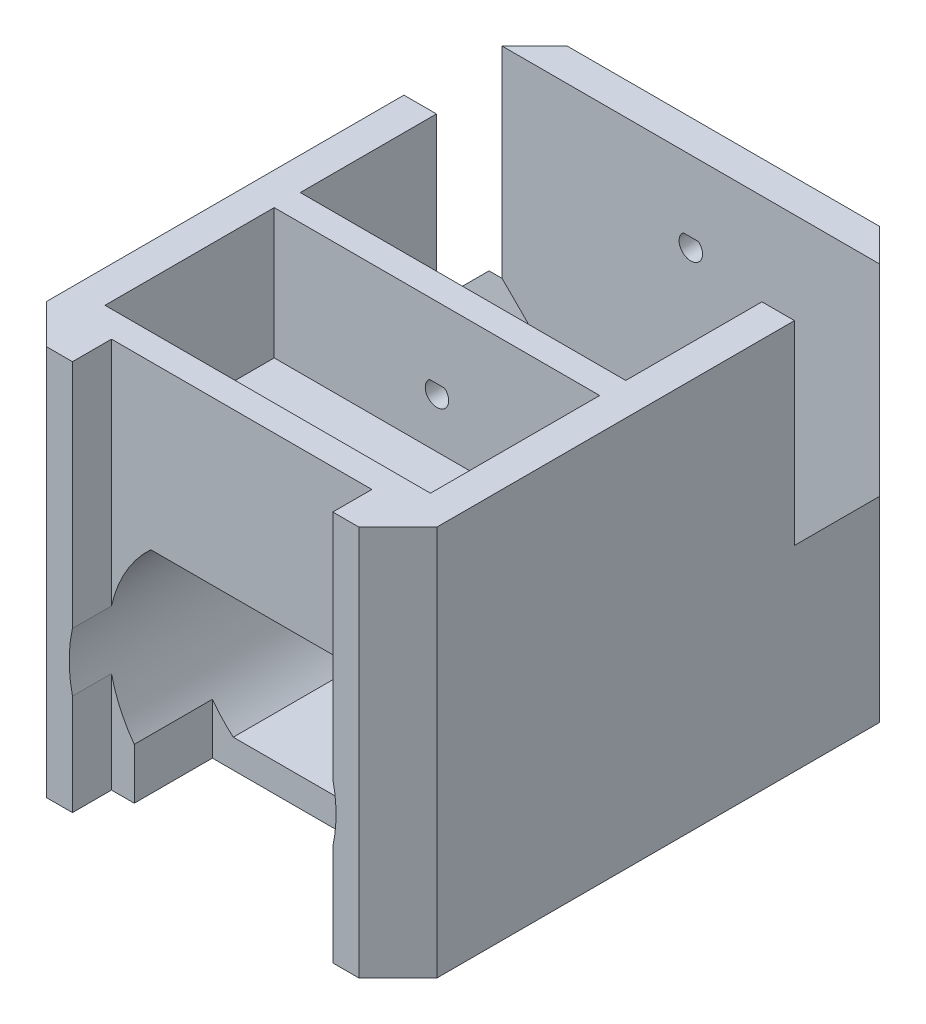
SolidWorks part; units mm, degrees
ref_plane "Front Plane" through (0, 0, 0) normal (0, 0, 1) x (1, 0, 0)
ref_plane "Top Plane" through (0, 0, 0) normal (0, 1, 0) x (1, 0, 0)
ref_plane "Right Plane" through (0, 0, 0) normal (1, 0, 0) x (0, 0, -1)
sketch "Sketch1" plane through (0, 0, 0) normal (0, 0, 1) x (1, 0, 0)
  line L1 (-15, -20) -> (15, -20)
  line L2 (-15, -20) -> (-15, 20)
  line L3 (-15, 20) -> (15, 20)
  line L4 (15, -20) -> (15, 20)
  line L5 (-15, -20) -> (15, 20) construction
  line L6 (-15, 20) -> (15, -20) construction
  point P0 (0, 0)
  dimension "D1" = 30
  dimension "D2" = 40
extrude "Boss-Extrude1" add sketch "Sketch1" along normal blind 40
sketch "Sketch2" plane through (0, 0, 40) normal (0, 0, 1) x (1, 0, 0)
  line L5 (-6.9866, -2.5) -> (6.9866, -2.5)
  line L7 (-6.6464, -17.803) -> (6.6464, -17.803)
  arc A4 (-6.9866, -2.5) -> (-6.6464, -17.803) centre (0, -10) ccw
  arc A5 (6.6464, -17.803) -> (6.9866, -2.5) centre (0, -10) ccw
  point P0 (0, -10)
  dimension "D2" = 20.5
extrude "Cut-Extrude1" cut sketch "Sketch2" against normal blind 35
sketch "Sketch4" plane through (0, 20, 0) normal (0, 1, 0) x (1, 0, 0)
  line L1 (-12.5, -37.5) -> (12.5, -37.5)
  line L2 (-12.5, -37.5) -> (-12.5, -2.5)
  line L3 (-12.5, -2.5) -> (12.5, -2.5)
  line L4 (12.5, -37.5) -> (12.5, -2.5)
  point P0 (0, -20)
  dimension "D1" = 25
  dimension "D2" = 35
extrude "Cut-Extrude3" cut sketch "Sketch4" against normal blind 20
sketch "Sketch5" plane through (0, 0, 0) normal (0, 1, 0) x (1, 0, 0)
  line L0 (12.5, -37.5) -> (12.5, -2.5) construction
  line L1 (-12.5, -2.5) -> (12.5, -2.5)
  line L2 (-12.5, -2.5) -> (-12.5, -20)
  line L3 (-12.5, -20) -> (12.5, -20)
  line L4 (12.5, -2.5) -> (12.5, -20)
extrude "Cut-Extrude4" cut sketch "Sketch5" against normal blind 20
sketch "Sketch13" plane through (0, 0, 0) normal (0, 1, 0) x (1, 0, 0)
  line L0 (12.5, -37.5) -> (12.5, -20) construction
  line L1 (-12.5, -20) -> (12.5, -20)
  line L2 (-12.5, -20) -> (-12.5, -22.0007)
  line L3 (-12.5, -22.0007) -> (12.5, -22.0007)
  line L4 (12.5, -20) -> (12.5, -22.0007)
extrude "Boss-Extrude3" add sketch "Sketch13" along normal up to surface (20 mm away) up to face at (0, 20, 20)
sketch "Sketch8" plane through (0, 0, 40) normal (0, 0, 1) x (1, 0, 0)
  line L0 (-0.5467, -9.1627) -> (0.5467, -9.1627)
  arc A3 (-0.5467, -9.1627) -> (0.5467, -9.1627) centre (0, -10.2278) ccw
extrude "Cut-Extrude5" cut sketch "Sketch8" against normal up to surface (40 mm away) up to face at (0, 0, 0)
sketch "Sketch9" plane through (0, 0, 0) normal (0, 0, -1) x (-1, 0, 0)
  line L5 (-0.5842, 4.5346) -> (0.5842, 4.5346)
  arc A0 (-0.5842, 4.5346) -> (0.5842, 4.5346) centre (0, 3.85) ccw
  dimension "D2" = 1.8
extrude "Cut-Extrude6" cut sketch "Sketch9" against normal up to surface (40 mm away) up to face at (0, -10.1897, 40)
sketch "Sketch10" plane through (0, 0, 40) normal (0, 0, 1) x (1, 0, 0)
  line L0 (15, -20) -> (15, 20) construction
  line L1 (-15, 20) -> (15, 20)
  line L2 (-15, 20) -> (-15, 10)
  line L3 (-15, 10) -> (15, 10)
  line L4 (15, 20) -> (15, 10)
  dimension "D1" = 10
extrude "Cut-Extrude9" cut sketch "Sketch10" against normal up to surface (40 mm away) up to face at (0, 3.7423, 0)
chamfer "Chamfer2" distance 3 angle 45 4 edges at (15, -5, 0) (15, -5, 40) (-15, -5, 40) (-15, -5, 0)
sketch "Sketch16" plane through (-12.5, 0, 0) normal (1, 0, 0) x (0, 0, -1)
  line L1 (-2.5, 10) -> (-9.5368, 10)
  line L2 (-2.5, 10) -> (-2.5, -4.4568)
  line L4 (-9.5368, 10) -> (-9.5368, -4.4568)
  line L5 (-9.5368, -4.4568) -> (-2.5, -4.4568)
extrude "Cut-Extrude10" cut sketch "Sketch16" against normal mid plane 57
chamfer "Chamfer3" distance 3 angle 45 2 edges at (12.5, -4.4568, 6.0184) (-12.5, -4.4568, 6.0184)
sketch "Sketch17" plane through (0, 10, 0) normal (0, 1, 0) x (1, 0, 0)
  line L0 (12.5, -37.5) -> (12.5, -22.0007) construction
  line L1 (-12.5, -37.5) -> (12.5, -37.5)
  line L2 (-12.5, -37.5) -> (-12.5, -35)
  line L3 (-12.5, -35) -> (12.5, -35)
  line L4 (12.5, -37.5) -> (12.5, -35)
  dimension "D1" = 2.5
extrude "Boss-Extrude4" add sketch "Sketch17" against normal up to surface (10 mm away) up to face at (0, 0, 29.7504)
sketch "Sketch18" plane through (0, 10, 0) normal (0, 1, 0) x (1, 0, 0)
  line L0 (-10, -40) -> (10, -40)
  line L1 (-12, -40) -> (12, -40) construction
  line L5 (-10, -40) -> (10, -40)
  line L6 (-10, -40) -> (-10, -37)
  line L7 (-10, -37) -> (10, -37)
  line L8 (10, -40) -> (10, -37)
  point P5 (0, -40)
  line M15 (-12, -40) -> (12, -40)
  dimension "D1" = 20
  dimension "D2" = 3
extrude "Cut-Extrude13" cut sketch "Sketch18" against normal up to surface (30 mm away) contours L8 L7 L6 M15 region at (0, 10, 38.5) up to face at (0, -20, 11.25)
sketch "Sketch19" plane through (0, -20, 0) normal (0, -1, 0) x (1, 0, 0)
  line L0 (-8.25, 37) -> (8.25, 37)
  line L1 (10, 37) -> (-10, 37) construction
  line L5 (-8.25, 37) -> (8.25, 37)
  line L6 (-8.25, 37) -> (-8.25, 31)
  line L7 (-8.25, 31) -> (8.25, 31)
  line L8 (8.25, 37) -> (8.25, 31)
  point P5 (0, 37)
  line M18 (10, 37) -> (-10, 37)
  dimension "D1" = 16.5
  dimension "D2" = 6
extrude "Cut-Extrude14" cut sketch "Sketch19" against normal blind 10 contours L8 L6 L7 M18 region at (0, -20, 34)
sketch "Sketch20" plane through (0, 0, 20) normal (0, 0, -1) x (-1, 0, 0)
  line L0 (10.25, -10) -> (12.5, -10)
  line L1 (-12.5, -10) -> (-10.25, -10)
  line L2 (-12.5, -10) -> (-12.5, -20)
  line L3 (-12.5, -20) -> (12.5, -20)
  line L4 (12.5, -20) -> (12.5, 10)
  line L5 (12.5, 10) -> (-12.5, 10)
  line L6 (-12.5, 10) -> (-12.5, -20)
  line L7 (-12.5, -20) -> (12.5, -20)
  line L8 (12.5, -20) -> (12.5, -10)
  line L10 (-12.5, -10) -> (-12.5, -20)
  line L11 (-12.5, -20) -> (12.5, -20)
  line L12 (12.5, -10) -> (12.5, -20)
  line L13 (-6.6464, -17.803) -> (6.6464, -17.803)
  arc A0 (6.6464, -17.803) -> (6.9866, -2.5) centre (0, -10) ccw construction
  arc A1 (6.6464, -17.803) -> (10.25, -10) centre (0, -10) ccw
  arc A2 (-6.9866, -2.5) -> (-6.6464, -17.803) centre (0, -10) ccw construction
  arc A3 (-10.25, -10) -> (-6.6464, -17.803) centre (0, -10) ccw
  line M7 (12.5, -20) -> (12.5, 10)
  line M9 (-12.5, 10) -> (-12.5, -20)
  line M10 (-12.5, -20) -> (12.5, -20)
  line M11 (6.6464, -17.803) -> (-6.6464, -17.803)
  arc M12 (-6.6464, -17.803) -> (-6.9866, -2.5) centre (0, -10) cw
  arc M14 (6.9866, -2.5) -> (6.6464, -17.803) centre (0, -10) cw
  dimension "D1" = 0
extrude "Boss-Extrude5" add sketch "Sketch20" along normal blind 8.5 contours L1 L0 M9 M10 M7 M14 M11 M12 region at (-11.375, -10.2693, 20)
sketch "Sketch22" plane through (0, 0, 11.5) normal (0, 0, -1) x (-1, 0, 0)
  line L0 (12.5, -20) -> (12.5, -10) construction
  line L1 (-12.5, -20) -> (12.5, -20)
  line L2 (-12.5, -20) -> (-12.5, -15)
  line L3 (-12.5, -15) -> (12.5, -15)
  line L4 (12.5, -20) -> (12.5, -15)
extrude "Boss-Extrude6" add sketch "Sketch22" along normal blind 1
